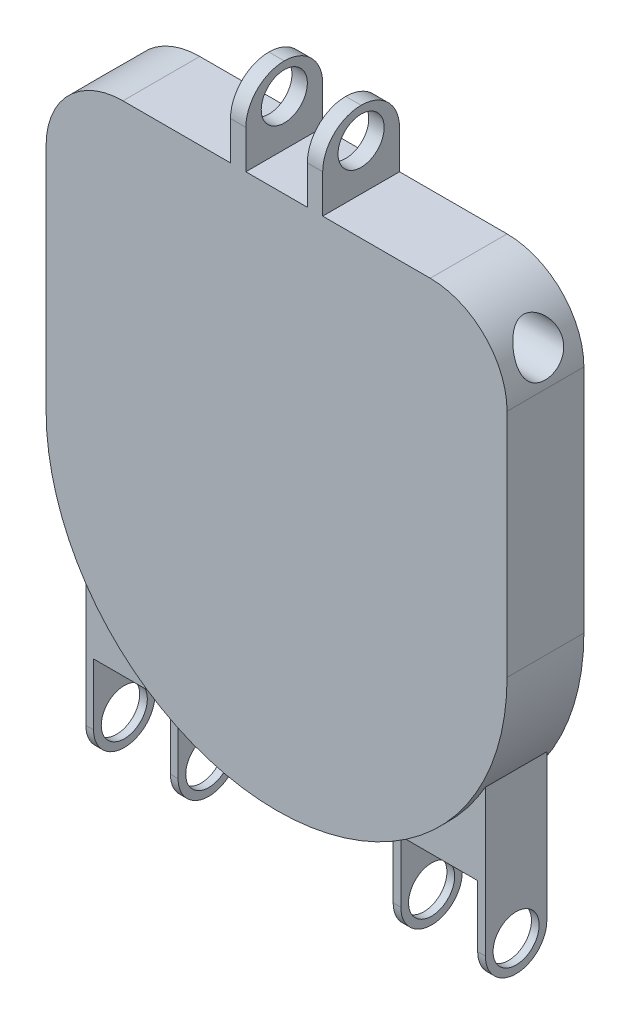
SolidWorks part; units mm, degrees
ref_plane "Front Plane" through (0, 0, 0) normal (0, 0, 1) x (1, 0, 0)
ref_plane "Top Plane" through (0, 0, 0) normal (0, 1, 0) x (1, 0, 0)
ref_plane "Right Plane" through (0, 0, 0) normal (1, 0, 0) x (0, 0, -1)
sketch "Sketch1" plane through (0, 0, 0) normal (0, 1, 0) x (1, 0, 0)
  line L1 (15, -2.5) -> (-15, -2.5)
  line L2 (15, -2.5) -> (15, 2.5)
  line L3 (15, 2.5) -> (-15, 2.5)
  line L4 (-15, -2.5) -> (-15, 2.5)
  line L5 (15, -2.5) -> (-15, 2.5) construction
  line L6 (15, 2.5) -> (-15, -2.5) construction
  point P0 (0, 0)
  dimension "D1" = 5
  dimension "D2" = 30
extrude "Boss-Extrude1" add sketch "Sketch1" along normal blind 35
fillet "Fillet1" radius 15 2 edges at (15, 0, 0) (-15, 0, 0)
fillet "Fillet3" radius 5 2 edges at (15, 35, 0) (-15, 35, 0)
sketch "Sketch4" plane through (-15, 0, 0) normal (-1, 0, 0) x (0, 0, 1)
  line L0 (0, 35) -> (0, 32)
  line L1 (-2.5, 35) -> (2.5, 35) construction
  circle A0 centre (0, 32) radius 1.5
extrude "Cut-Extrude1" cut sketch "Sketch4" against normal blind 35 contours A0 region at (-15, 30.9693, -1.0307)
sketch "Sketch5" plane through (0, 35, 0) normal (0, 1, 0) x (1, 0, 0)
  line L0 (-2, 1.5) -> (-2, -1.5)
  line L1 (3, 2.5) -> (-3, 2.5)
  line L2 (3, 2.5) -> (3, -2.5)
  line L3 (3, -2.5) -> (-3, -2.5)
  line L4 (-3, 2.5) -> (-3, -2.5)
  line L5 (3, 2.5) -> (-3, -2.5) construction
  line L6 (3, -2.5) -> (-3, 2.5) construction
  line L7 (2, -1.5) -> (-2, -1.5)
  line L8 (2, 1.5) -> (2, -1.5)
  line L9 (2, 1.5) -> (-2, 1.5)
  point P0 (0, 0)
  dimension "D1" = 5
  dimension "D3" = 6
  dimension "D2" = 1
extrude "Boss-Extrude2" add sketch "Sketch5" along normal blind 5
sketch "Sketch6" plane through (0, 40, 0) normal (0, 1, 0) x (1, 0, 0)
  line L0 (-2, 1.5) -> (-2, 3.8605)
  line L1 (-2, 3.8605) -> (2, 3.8605)
  line L2 (2, 3.8605) -> (2, -3.4179)
  line L3 (2, -3.4179) -> (-2, -3.4179)
  line L4 (-2, -3.4179) -> (-2, 1.5)
  dimension "D1" = 4
extrude "Cut-Extrude2" cut sketch "Sketch6" against normal blind 5
sketch "Sketch7" plane through (-3, 0, 0) normal (-1, 0, 0) x (0, 0, 1)
  line L2 (0, 35) -> (0, 36.5)
  line L3 (-2.5, 35) -> (2.5, 35) construction
  circle A0 centre (0, 38) radius 1.5
  point P10 (0, 37.8506)
extrude "Cut-Extrude3" cut sketch "Sketch7" against normal blind 15 contours A0 region at (-3, 38, 0)
fillet "Fillet4" radius 2.5 4 edges at (-2.5, 40, 2.5) (-2.5, 40, -2.5) (2.5, 40, 2.5) (2.5, 40, -2.5)
sketch "Sketch8" plane through (0, 0, 0) normal (0, 1, 0) x (1, 0, 0)
  line L0 (-15, 0) -> (-13, 0)
  line L1 (-15, 2.5) -> (-15, -2.5) construction
  line L2 (15, 0) -> (13, 0)
  line L3 (15, -2.5) -> (15, 2.5) construction
  line L4 (-13, -1.9122) -> (-13, 2.0878)
  line L5 (-13, 2.0878) -> (-7, 2.0878)
  line L6 (-7, 2.0878) -> (-7, -1.9122)
  line L7 (-7, -1.9122) -> (-13, -1.9122)
  line L8 (0, -2.5) -> (0, 2.5) construction
  line L9 (7, -1.9122) -> (13, -1.9122)
  line L10 (7, 2.0878) -> (7, -1.9122)
  line L11 (13, 2.0878) -> (7, 2.0878)
  line L12 (13, -1.9122) -> (13, 2.0878)
  line L13 (-7.5, -1.4122) -> (-12.5, -1.4122)
  line L14 (-12.5, -1.4122) -> (-12.5, 1.5878)
  line L15 (-12.5, 1.5878) -> (-7.5, 1.5878)
  line L16 (-7.5, 1.5878) -> (-7.5, -1.4122)
  line L17 (7.5, -1.4122) -> (12.5, -1.4122)
  line L18 (12.5, -1.4122) -> (12.5, 1.5878)
  line L19 (12.5, 1.5878) -> (7.5, 1.5878)
  line L20 (7.5, 1.5878) -> (7.5, -1.4122)
  dimension "D1" = 6
  dimension "D2" = 4
  dimension "D3" = 0.5
extrude "Boss-Extrude3" add sketch "Sketch8" along normal blind 8 and the other way blind 4 contours L7 L6 L5 L4 L15 L16 L13 L14 | L9 L12 L11 L10 L20 L19 L18 L17 region at (-12.9279, 0, 0.9561) region at (7.0721, 0, -0.0878)
sketch "Sketch9" plane through (0, -4, 0) normal (0, -1, 0) x (1, 0, 0)
  line L0 (-12.5, 2.1475) -> (-12.5, -2.37)
  line L1 (-12.5, -2.37) -> (-7.5, -2.37)
  line L2 (-7.5, -2.37) -> (-7.5, 2.1475)
  line L3 (-7.5, 2.1475) -> (-12.5, 2.1475)
  line L4 (0, 2.5) -> (0, -2.5) construction
  line L5 (12.5, -2.37) -> (7.5, -2.37)
  line L6 (7.5, -2.37) -> (7.5, 2.1475)
  line L7 (7.5, 2.1475) -> (12.5, 2.1475)
  line L8 (12.5, 2.1475) -> (12.5, -2.37)
extrude "Cut-Extrude4" cut sketch "Sketch9" against normal blind 6
sketch "Sketch10" plane through (-13, 0, 0) normal (-1, 0, 0) x (0, 0, 1)
  line L0 (-0.0878, -4) -> (-0.0878, -2)
  line L1 (1.9122, -4) -> (-2.0878, -4) construction
  circle A0 centre (-0.0878, -2) radius 1.5
extrude "Cut-Extrude5" cut sketch "Sketch10" against normal blind 36 contours A0 region at (-13, -3.0307, 0.9429)
fillet "Fillet5" radius 2 4 edges at (7.25, -4, -2.0878) (7.25, -4, 1.9122) (12.75, -4, 1.9122) (12.75, -4, -2.0878)
fillet "Fillet6" radius 2 4 edges at (-7.25, -4, 1.9122) (-12.75, -4, 1.9122) (-12.75, -4, -2.0878) (-7.25, -4, -2.0878)
